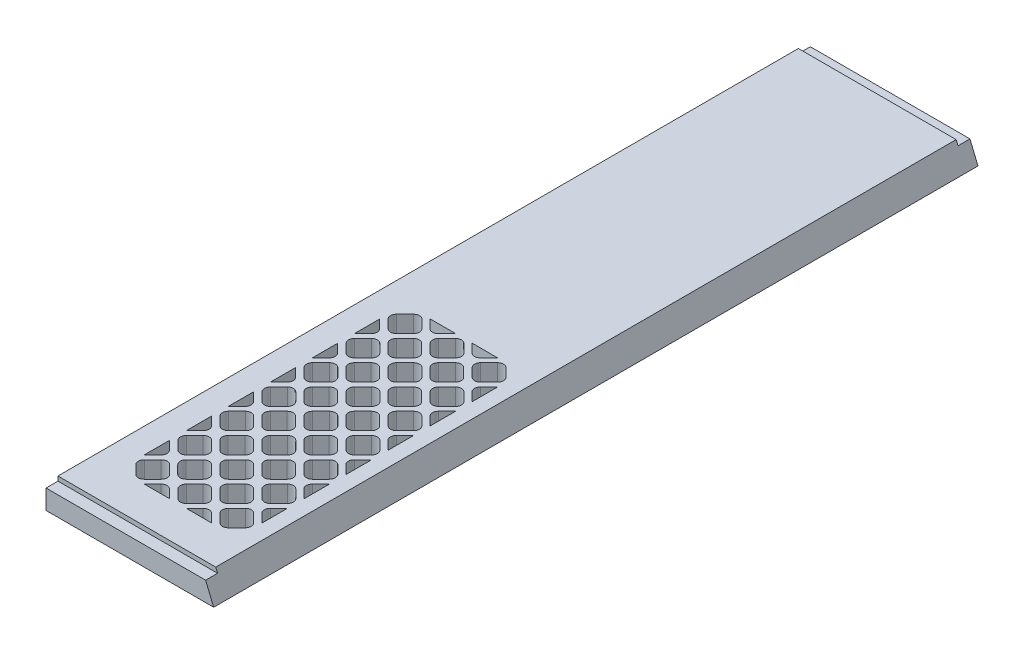
SolidWorks part; units mm, degrees
ref_plane "Front Plane" through (0, 0, 0) normal (0, 0, 1) x (1, 0, 0)
ref_plane "Top Plane" through (0, 0, 0) normal (0, 1, 0) x (1, 0, 0)
ref_plane "Right Plane" through (0, 0, 0) normal (1, 0, 0) x (0, 0, -1)
sketch "Sketch1" plane through (0, 0, 0) normal (0, 0, 1) x (1, 0, 0)
  line L0 (0, 0) -> (0, 12.7)
  line L1 (0, 12.7) -> (83.8935, 12.7)
  line L2 (83.8935, 12.7) -> (89.154, 0)
  line L3 (89.154, 0) -> (0, 0)
  dimension "D1" = 12.7
  dimension "D2" = 67.5
  dimension "D3" = 89.154
extrude "Boss-Extrude1" add sketch "Sketch1" along normal blind 406.4
sketch "Sketch2" plane through (0, 12.7, 0) normal (0, -1, 0) x (1, 0, 0)
  line L0 (0, 406.4) -> (0, 0) construction
  line L1 (0, 6.35) -> (89.154, 6.35)
  line L2 (0, 6.35) -> (0, 0)
  line L3 (0, 0) -> (89.154, 0)
  line L4 (89.154, 6.35) -> (89.154, 0)
  line L5 (89.154, 406.4) -> (89.154, 0) construction
  line L6 (0, 406.4) -> (89.154, 406.4)
  line L7 (0, 406.4) -> (0, 400.05)
  line L8 (0, 400.05) -> (89.154, 400.05)
  line L9 (89.154, 406.4) -> (89.154, 400.05)
  dimension "D1" = 6.35
  dimension "D2" = 6.35
extrude "Cut-Extrude1" cut sketch "Sketch2" along normal blind 2.3622
sketch "Sketch3" plane through (0, 0, 0) normal (0, -1, 0) x (1, 0, 0)
  line L0 (15.4898, 374.1011) -> (19.9799, 378.5912)
  line L1 (13.2447, 380.8363) -> (75.9093, 380.8363)
  line L2 (13.2447, 380.8363) -> (13.2447, 228.7637)
  line L3 (13.2447, 228.7637) -> (75.9093, 228.7637)
  line L4 (75.9093, 380.8363) -> (75.9093, 228.7637)
  line L5 (24.4701, 378.5912) -> (28.9602, 374.1011)
  line L6 (28.9602, 369.6109) -> (24.4701, 365.1208)
  line L7 (19.9799, 365.1208) -> (15.4898, 369.6109)
  line L8 (42.3319, 365.1208) -> (37.8418, 369.6109)
  line L9 (37.8418, 374.1011) -> (42.3319, 378.5912)
  line L10 (46.8221, 378.5912) -> (51.3122, 374.1011)
  line L11 (51.3122, 369.6109) -> (46.8221, 365.1208)
  line L12 (64.6839, 365.1208) -> (60.1938, 369.6109)
  line L13 (60.1938, 374.1011) -> (64.6839, 378.5912)
  line L14 (69.1741, 378.5912) -> (73.6642, 374.1011)
  line L15 (73.6642, 369.6109) -> (69.1741, 365.1208)
  line L16 (19.9799, 342.7688) -> (15.4898, 347.2589)
  line L17 (15.4898, 351.7491) -> (19.9799, 356.2392)
  line L18 (24.4701, 356.2392) -> (28.9602, 351.7491)
  line L19 (28.9602, 347.2589) -> (24.4701, 342.7688)
  line L20 (42.3319, 342.7688) -> (37.8418, 347.2589)
  line L21 (37.8418, 351.7491) -> (42.3319, 356.2392)
  line L22 (46.8221, 356.2392) -> (51.3122, 351.7491)
  line L23 (51.3122, 347.2589) -> (46.8221, 342.7688)
  line L24 (64.6839, 342.7688) -> (60.1938, 347.2589)
  line L25 (60.1938, 351.7491) -> (64.6839, 356.2392)
  line L26 (69.1741, 356.2392) -> (73.6642, 351.7491)
  line L27 (73.6642, 347.2589) -> (69.1741, 342.7688)
  line L28 (19.9799, 320.4168) -> (15.4898, 324.9069)
  line L29 (15.4898, 329.3971) -> (19.9799, 333.8872)
  line L30 (24.4701, 333.8872) -> (28.9602, 329.3971)
  line L31 (28.9602, 324.9069) -> (24.4701, 320.4168)
  line L32 (42.3319, 320.4168) -> (37.8418, 324.9069)
  line L33 (37.8418, 329.3971) -> (42.3319, 333.8872)
  line L34 (46.8221, 333.8872) -> (51.3122, 329.3971)
  line L35 (51.3122, 324.9069) -> (46.8221, 320.4168)
  line L36 (64.6839, 320.4168) -> (60.1938, 324.9069)
  line L37 (60.1938, 329.3971) -> (64.6839, 333.8872)
  line L38 (69.1741, 333.8872) -> (73.6642, 329.3971)
  line L39 (73.6642, 324.9069) -> (69.1741, 320.4168)
  line L40 (19.9799, 298.0648) -> (15.4898, 302.5549)
  line L41 (15.4898, 307.0451) -> (19.9799, 311.5352)
  line L42 (24.4701, 311.5352) -> (28.9602, 307.0451)
  line L43 (28.9602, 302.5549) -> (24.4701, 298.0648)
  line L44 (42.3319, 298.0648) -> (37.8418, 302.5549)
  line L45 (37.8418, 307.0451) -> (42.3319, 311.5352)
  line L46 (46.8221, 311.5352) -> (51.3122, 307.0451)
  line L47 (51.3122, 302.5549) -> (46.8221, 298.0648)
  line L48 (64.6839, 298.0648) -> (60.1938, 302.5549)
  line L49 (60.1938, 307.0451) -> (64.6839, 311.5352)
  line L50 (69.1741, 311.5352) -> (73.6642, 307.0451)
  line L51 (73.6642, 302.5549) -> (69.1741, 298.0648)
  line L52 (19.9799, 275.7128) -> (15.4898, 280.2029)
  line L53 (15.4898, 284.6931) -> (19.9799, 289.1832)
  line L54 (24.4701, 289.1832) -> (28.9602, 284.6931)
  line L55 (28.9602, 280.2029) -> (24.4701, 275.7128)
  line L56 (42.3319, 275.7128) -> (37.8418, 280.2029)
  line L57 (37.8418, 284.6931) -> (42.3319, 289.1832)
  line L58 (46.8221, 289.1832) -> (51.3122, 284.6931)
  line L59 (51.3122, 280.2029) -> (46.8221, 275.7128)
  line L60 (64.6839, 275.7128) -> (60.1938, 280.2029)
  line L61 (60.1938, 284.6931) -> (64.6839, 289.1832)
  line L62 (69.1741, 289.1832) -> (73.6642, 284.6931)
  line L63 (73.6642, 280.2029) -> (69.1741, 275.7128)
  line L64 (19.9799, 253.3608) -> (15.4898, 257.8509)
  line L65 (15.4898, 262.3411) -> (19.9799, 266.8312)
  line L66 (24.4701, 266.8312) -> (28.9602, 262.3411)
  line L67 (28.9602, 257.8509) -> (24.4701, 253.3608)
  line L68 (42.3319, 253.3608) -> (37.8418, 257.8509)
  line L69 (37.8418, 262.3411) -> (42.3319, 266.8312)
  line L70 (46.8221, 266.8312) -> (51.3122, 262.3411)
  line L71 (51.3122, 257.8509) -> (46.8221, 253.3608)
  line L72 (64.6839, 253.3608) -> (60.1938, 257.8509)
  line L73 (60.1938, 262.3411) -> (64.6839, 266.8312)
  line L74 (69.1741, 266.8312) -> (73.6642, 262.3411)
  line L75 (73.6642, 257.8509) -> (69.1741, 253.3608)
  line L76 (19.9799, 231.0088) -> (15.4898, 235.4989)
  line L77 (15.4898, 239.9891) -> (19.9799, 244.4792)
  line L78 (24.4701, 244.4792) -> (28.9602, 239.9891)
  line L79 (28.9602, 235.4989) -> (24.4701, 231.0088)
  line L80 (42.3319, 231.0088) -> (37.8418, 235.4989)
  line L81 (37.8418, 239.9891) -> (42.3319, 244.4792)
  line L82 (46.8221, 244.4792) -> (51.3122, 239.9891)
  line L83 (51.3122, 235.4989) -> (46.8221, 231.0088)
  line L84 (64.6839, 231.0088) -> (60.1938, 235.4989)
  line L85 (60.1938, 239.9891) -> (64.6839, 244.4792)
  line L86 (69.1741, 244.4792) -> (73.6642, 239.9891)
  line L87 (73.6642, 235.4989) -> (69.1741, 231.0088)
  line L91 (0, 400.05) -> (89.154, 400.05) construction
  line L92 (13.2447, 376.3461) -> (17.7349, 380.8363)
  line L98 (35.5967, 376.3461) -> (40.0869, 380.8363)
  line L99 (31.1066, 376.3461) -> (26.6165, 380.8363)
  line L102 (57.9487, 376.3461) -> (62.4389, 380.8363)
  line L103 (53.4586, 376.3461) -> (48.9685, 380.8363)
  line L107 (75.8106, 376.3461) -> (71.3205, 380.8363)
  line L108 (26.6165, 362.9744) -> (31.1066, 367.4645)
  line L109 (40.0869, 362.9744) -> (35.5967, 367.4645)
  line L110 (35.5967, 353.9941) -> (40.0869, 358.4843)
  line L111 (31.1066, 353.9941) -> (26.6165, 358.4843)
  line L112 (48.9685, 362.9744) -> (53.4586, 367.4645)
  line L113 (62.4389, 362.9744) -> (57.9487, 367.4645)
  line L114 (57.9487, 353.9941) -> (62.4389, 358.4843)
  line L115 (53.4586, 353.9941) -> (48.9685, 358.4843)
  line L116 (71.3205, 362.9744) -> (75.8106, 367.4645)
  line L119 (75.8106, 353.9941) -> (71.3205, 358.4843)
  line L120 (26.6165, 340.6224) -> (31.1066, 345.1125)
  line L121 (40.0869, 340.6224) -> (35.5967, 345.1125)
  line L122 (35.5967, 331.6421) -> (40.0869, 336.1323)
  line L123 (31.1066, 331.6421) -> (26.6165, 336.1323)
  line L124 (48.9685, 340.6224) -> (53.4586, 345.1125)
  line L125 (62.4389, 340.6224) -> (57.9487, 345.1125)
  line L126 (57.9487, 331.6421) -> (62.4389, 336.1323)
  line L127 (53.4586, 331.6421) -> (48.9685, 336.1323)
  line L128 (71.3205, 340.6224) -> (75.8106, 345.1125)
  line L131 (75.8106, 331.6421) -> (71.3205, 336.1323)
  line L132 (26.6165, 318.2704) -> (31.1066, 322.7605)
  line L133 (40.0869, 318.2704) -> (35.5967, 322.7605)
  line L134 (35.5967, 309.2901) -> (40.0869, 313.7803)
  line L135 (31.1066, 309.2901) -> (26.6165, 313.7803)
  line L136 (48.9685, 318.2704) -> (53.4586, 322.7605)
  line L137 (62.4389, 318.2704) -> (57.9487, 322.7605)
  line L138 (57.9487, 309.2901) -> (62.4389, 313.7803)
  line L139 (53.4586, 309.2901) -> (48.9685, 313.7803)
  line L140 (71.3205, 318.2704) -> (75.8106, 322.7605)
  line L143 (75.8106, 309.2901) -> (71.3205, 313.7803)
  line L144 (26.6165, 295.9184) -> (31.1066, 300.4085)
  line L145 (40.0869, 295.9184) -> (35.5967, 300.4085)
  line L146 (35.5967, 286.9381) -> (40.0869, 291.4283)
  line L147 (31.1066, 286.9381) -> (26.6165, 291.4283)
  line L148 (48.9685, 295.9184) -> (53.4586, 300.4085)
  line L149 (62.4389, 295.9184) -> (57.9487, 300.4085)
  line L150 (57.9487, 286.9381) -> (62.4389, 291.4283)
  line L151 (53.4586, 286.9381) -> (48.9685, 291.4283)
  line L152 (71.3205, 295.9184) -> (75.8106, 300.4085)
  line L155 (75.8106, 286.9381) -> (71.3205, 291.4283)
  line L156 (26.6165, 273.5664) -> (31.1066, 278.0565)
  line L157 (40.0869, 273.5664) -> (35.5967, 278.0565)
  line L158 (35.5967, 264.5861) -> (40.0869, 269.0763)
  line L159 (31.1066, 264.5861) -> (26.6165, 269.0763)
  line L160 (48.9685, 273.5664) -> (53.4586, 278.0565)
  line L161 (62.4389, 273.5664) -> (57.9487, 278.0565)
  line L162 (57.9487, 264.5861) -> (62.4389, 269.0763)
  line L163 (53.4586, 264.5861) -> (48.9685, 269.0763)
  line L164 (71.3205, 273.5664) -> (75.8106, 278.0565)
  line L167 (75.8106, 264.5861) -> (71.3205, 269.0763)
  line L168 (26.6165, 251.2144) -> (31.1066, 255.7045)
  line L169 (40.0869, 251.2144) -> (35.5967, 255.7045)
  line L170 (35.5967, 242.2341) -> (40.0869, 246.7243)
  line L171 (31.1066, 242.2341) -> (26.6165, 246.7243)
  line L172 (48.9685, 251.2144) -> (53.4586, 255.7045)
  line L173 (62.4389, 251.2144) -> (57.9487, 255.7045)
  line L174 (57.9487, 242.2341) -> (62.4389, 246.7243)
  line L175 (53.4586, 242.2341) -> (48.9685, 246.7243)
  line L176 (71.3205, 251.2144) -> (75.8106, 255.7045)
  line L179 (75.8106, 242.2341) -> (71.3205, 246.7243)
  line L180 (26.6165, 228.8624) -> (31.1066, 233.3525)
  line L181 (40.0869, 228.8624) -> (35.5967, 233.3525)
  line L184 (48.9685, 228.8624) -> (53.4586, 233.3525)
  line L185 (62.4389, 228.8624) -> (57.9487, 233.3525)
  line L188 (71.3205, 228.8624) -> (75.8106, 233.3525)
  line L193 (17.7349, 362.9744) -> (13.2447, 367.4645)
  line L194 (13.2447, 353.9941) -> (17.7349, 358.4843)
  line L197 (17.7349, 340.6224) -> (13.2447, 345.1125)
  line L198 (13.2447, 331.6421) -> (17.7349, 336.1323)
  line L201 (17.7349, 318.2704) -> (13.2447, 322.7605)
  line L202 (13.2447, 309.2901) -> (17.7349, 313.7803)
  line L205 (17.7349, 295.9184) -> (13.2447, 300.4085)
  line L206 (13.2447, 286.9381) -> (17.7349, 291.4283)
  line L209 (17.7349, 273.5664) -> (13.2447, 278.0565)
  line L210 (13.2447, 264.5861) -> (17.7349, 269.0763)
  line L213 (17.7349, 251.2144) -> (13.2447, 255.7045)
  line L214 (13.2447, 242.2341) -> (17.7349, 246.7243)
  line L217 (17.7349, 228.8624) -> (13.2447, 233.3525)
  line L220 (80.3007, 376.3461) -> (84.7909, 380.8363) [skipped]
  line L221 (80.3007, 353.9941) -> (84.7909, 358.4843) [skipped]
  line L222 (80.3007, 331.6421) -> (84.7909, 336.1323) [skipped]
  line L223 (80.3007, 309.2901) -> (84.7909, 313.7803) [skipped]
  line L224 (80.3007, 286.9381) -> (84.7909, 291.4283) [skipped]
  line L225 (80.3007, 264.5861) -> (84.7909, 269.0763) [skipped]
  line L226 (80.3007, 242.2341) -> (84.7909, 246.7243) [skipped]
  line L227 (80.3007, 219.8821) -> (84.7909, 224.3723) [skipped]
  line L228 (57.9487, 219.8821) -> (62.4389, 224.3723) [skipped]
  line L229 (35.5967, 219.8821) -> (40.0869, 224.3723) [skipped]
  line L230 (13.2447, 219.8821) -> (17.7349, 224.3723) [skipped]
  arc A0 (24.4701, 365.1208) -> (19.9799, 365.1208) centre (22.225, 367.3659) cw
  arc A1 (28.9602, 374.1011) -> (28.9602, 369.6109) centre (26.7151, 371.856) cw
  arc A2 (15.4898, 374.1011) -> (15.4898, 369.6109) centre (17.7349, 371.856) ccw
  arc A3 (19.9799, 378.5912) -> (24.4701, 378.5912) centre (22.225, 376.3461) cw
  arc A4 (37.8418, 374.1011) -> (37.8418, 369.6109) centre (40.0869, 371.856) ccw
  arc A5 (46.8221, 365.1208) -> (42.3319, 365.1208) centre (44.577, 367.3659) cw
  arc A6 (42.3319, 378.5912) -> (46.8221, 378.5912) centre (44.577, 376.3461) cw
  arc A7 (51.3122, 374.1011) -> (51.3122, 369.6109) centre (49.0671, 371.856) cw
  arc A8 (60.1938, 374.1011) -> (60.1938, 369.6109) centre (62.4389, 371.856) ccw
  arc A9 (69.1741, 365.1208) -> (64.6839, 365.1208) centre (66.929, 367.3659) cw
  arc A10 (64.6839, 378.5912) -> (69.1741, 378.5912) centre (66.929, 376.3461) cw
  arc A11 (73.6642, 374.1011) -> (73.6642, 369.6109) centre (71.4191, 371.856) cw
  arc A12 (15.4898, 351.7491) -> (15.4898, 347.2589) centre (17.7349, 349.504) ccw
  arc A13 (24.4701, 342.7688) -> (19.9799, 342.7688) centre (22.225, 345.0139) cw
  arc A14 (19.9799, 356.2392) -> (24.4701, 356.2392) centre (22.225, 353.9941) cw
  arc A15 (28.9602, 351.7491) -> (28.9602, 347.2589) centre (26.7151, 349.504) cw
  arc A16 (37.8418, 351.7491) -> (37.8418, 347.2589) centre (40.0869, 349.504) ccw
  arc A17 (42.3319, 356.2392) -> (46.8221, 356.2392) centre (44.577, 353.9941) cw
  arc A18 (51.3122, 351.7491) -> (51.3122, 347.2589) centre (49.0671, 349.504) cw
  arc A19 (46.8221, 342.7688) -> (42.3319, 342.7688) centre (44.577, 345.0139) cw
  arc A20 (60.1938, 351.7491) -> (60.1938, 347.2589) centre (62.4389, 349.504) ccw
  arc A21 (64.6839, 356.2392) -> (69.1741, 356.2392) centre (66.929, 353.9941) cw
  arc A22 (73.6642, 351.7491) -> (73.6642, 347.2589) centre (71.4191, 349.504) cw
  arc A23 (69.1741, 342.7688) -> (64.6839, 342.7688) centre (66.929, 345.0139) cw
  arc A24 (15.4898, 329.3971) -> (15.4898, 324.9069) centre (17.7349, 327.152) ccw
  arc A25 (24.4701, 320.4168) -> (19.9799, 320.4168) centre (22.225, 322.6619) cw
  arc A26 (19.9799, 333.8872) -> (24.4701, 333.8872) centre (22.225, 331.6421) cw
  arc A27 (28.9602, 329.3971) -> (28.9602, 324.9069) centre (26.7151, 327.152) cw
  arc A28 (37.8418, 329.3971) -> (37.8418, 324.9069) centre (40.0869, 327.152) ccw
  arc A29 (42.3319, 333.8872) -> (46.8221, 333.8872) centre (44.577, 331.6421) cw
  arc A30 (51.3122, 329.3971) -> (51.3122, 324.9069) centre (49.0671, 327.152) cw
  arc A31 (46.8221, 320.4168) -> (42.3319, 320.4168) centre (44.577, 322.6619) cw
  arc A32 (60.1938, 329.3971) -> (60.1938, 324.9069) centre (62.4389, 327.152) ccw
  arc A33 (64.6839, 333.8872) -> (69.1741, 333.8872) centre (66.929, 331.6421) cw
  arc A34 (73.6642, 329.3971) -> (73.6642, 324.9069) centre (71.4191, 327.152) cw
  arc A35 (69.1741, 320.4168) -> (64.6839, 320.4168) centre (66.929, 322.6619) cw
  arc A36 (15.4898, 307.0451) -> (15.4898, 302.5549) centre (17.7349, 304.8) ccw
  arc A37 (24.4701, 298.0648) -> (19.9799, 298.0648) centre (22.225, 300.3099) cw
  arc A38 (19.9799, 311.5352) -> (24.4701, 311.5352) centre (22.225, 309.2901) cw
  arc A39 (28.9602, 307.0451) -> (28.9602, 302.5549) centre (26.7151, 304.8) cw
  arc A40 (37.8418, 307.0451) -> (37.8418, 302.5549) centre (40.0869, 304.8) ccw
  arc A41 (42.3319, 311.5352) -> (46.8221, 311.5352) centre (44.577, 309.2901) cw
  arc A42 (51.3122, 307.0451) -> (51.3122, 302.5549) centre (49.0671, 304.8) cw
  arc A43 (46.8221, 298.0648) -> (42.3319, 298.0648) centre (44.577, 300.3099) cw
  arc A44 (60.1938, 307.0451) -> (60.1938, 302.5549) centre (62.4389, 304.8) ccw
  arc A45 (64.6839, 311.5352) -> (69.1741, 311.5352) centre (66.929, 309.2901) cw
  arc A46 (73.6642, 307.0451) -> (73.6642, 302.5549) centre (71.4191, 304.8) cw
  arc A47 (69.1741, 298.0648) -> (64.6839, 298.0648) centre (66.929, 300.3099) cw
  arc A48 (15.4898, 284.6931) -> (15.4898, 280.2029) centre (17.7349, 282.448) ccw
  arc A49 (24.4701, 275.7128) -> (19.9799, 275.7128) centre (22.225, 277.9579) cw
  arc A50 (19.9799, 289.1832) -> (24.4701, 289.1832) centre (22.225, 286.9381) cw
  arc A51 (28.9602, 284.6931) -> (28.9602, 280.2029) centre (26.7151, 282.448) cw
  arc A52 (37.8418, 284.6931) -> (37.8418, 280.2029) centre (40.0869, 282.448) ccw
  arc A53 (42.3319, 289.1832) -> (46.8221, 289.1832) centre (44.577, 286.9381) cw
  arc A54 (51.3122, 284.6931) -> (51.3122, 280.2029) centre (49.0671, 282.448) cw
  arc A55 (46.8221, 275.7128) -> (42.3319, 275.7128) centre (44.577, 277.9579) cw
  arc A56 (60.1938, 284.6931) -> (60.1938, 280.2029) centre (62.4389, 282.448) ccw
  arc A57 (64.6839, 289.1832) -> (69.1741, 289.1832) centre (66.929, 286.9381) cw
  arc A58 (73.6642, 284.6931) -> (73.6642, 280.2029) centre (71.4191, 282.448) cw
  arc A59 (69.1741, 275.7128) -> (64.6839, 275.7128) centre (66.929, 277.9579) cw
  arc A60 (15.4898, 262.3411) -> (15.4898, 257.8509) centre (17.7349, 260.096) ccw
  arc A61 (24.4701, 253.3608) -> (19.9799, 253.3608) centre (22.225, 255.6059) cw
  arc A62 (19.9799, 266.8312) -> (24.4701, 266.8312) centre (22.225, 264.5861) cw
  arc A63 (28.9602, 262.3411) -> (28.9602, 257.8509) centre (26.7151, 260.096) cw
  arc A64 (37.8418, 262.3411) -> (37.8418, 257.8509) centre (40.0869, 260.096) ccw
  arc A65 (42.3319, 266.8312) -> (46.8221, 266.8312) centre (44.577, 264.5861) cw
  arc A66 (51.3122, 262.3411) -> (51.3122, 257.8509) centre (49.0671, 260.096) cw
  arc A67 (46.8221, 253.3608) -> (42.3319, 253.3608) centre (44.577, 255.6059) cw
  arc A68 (60.1938, 262.3411) -> (60.1938, 257.8509) centre (62.4389, 260.096) ccw
  arc A69 (64.6839, 266.8312) -> (69.1741, 266.8312) centre (66.929, 264.5861) cw
  arc A70 (73.6642, 262.3411) -> (73.6642, 257.8509) centre (71.4191, 260.096) cw
  arc A71 (69.1741, 253.3608) -> (64.6839, 253.3608) centre (66.929, 255.6059) cw
  arc A72 (15.4898, 239.9891) -> (15.4898, 235.4989) centre (17.7349, 237.744) ccw
  arc A73 (24.4701, 231.0088) -> (19.9799, 231.0088) centre (22.225, 233.2539) cw
  arc A74 (19.9799, 244.4792) -> (24.4701, 244.4792) centre (22.225, 242.2341) cw
  arc A75 (28.9602, 239.9891) -> (28.9602, 235.4989) centre (26.7151, 237.744) cw
  arc A76 (37.8418, 239.9891) -> (37.8418, 235.4989) centre (40.0869, 237.744) ccw
  arc A77 (42.3319, 244.4792) -> (46.8221, 244.4792) centre (44.577, 242.2341) cw
  arc A78 (51.3122, 239.9891) -> (51.3122, 235.4989) centre (49.0671, 237.744) cw
  arc A79 (46.8221, 231.0088) -> (42.3319, 231.0088) centre (44.577, 233.2539) cw
  arc A80 (60.1938, 239.9891) -> (60.1938, 235.4989) centre (62.4389, 237.744) ccw
  arc A81 (64.6839, 244.4792) -> (69.1741, 244.4792) centre (66.929, 242.2341) cw
  arc A82 (73.6642, 239.9891) -> (73.6642, 235.4989) centre (71.4191, 237.744) cw
  arc A83 (69.1741, 231.0088) -> (64.6839, 231.0088) centre (66.929, 233.2539) cw
  arc A91 (35.5967, 376.3461) -> (31.1066, 376.3461) centre (33.3517, 378.5912) cw
  arc A95 (57.9487, 376.3461) -> (53.4586, 376.3461) centre (55.7037, 378.5912) cw
  arc A99 (75.9093, 376.2516) -> (75.8106, 376.3461) centre (78.0557, 378.5912) cw
  arc A100 (35.5967, 367.4645) -> (31.1066, 367.4645) centre (33.3517, 365.2194) ccw
  arc A101 (26.6165, 358.4843) -> (26.6165, 362.9744) centre (28.8616, 360.7293) cw
  arc A102 (40.0869, 358.4843) -> (40.0869, 362.9744) centre (37.8418, 360.7293) ccw
  arc A103 (35.5967, 353.9941) -> (31.1066, 353.9941) centre (33.3517, 356.2392) cw
  arc A104 (57.9487, 367.4645) -> (53.4586, 367.4645) centre (55.7037, 365.2194) ccw
  arc A105 (48.9685, 358.4843) -> (48.9685, 362.9744) centre (51.2136, 360.7293) cw
  arc A106 (62.4389, 358.4843) -> (62.4389, 362.9744) centre (60.1938, 360.7293) ccw
  arc A107 (57.9487, 353.9941) -> (53.4586, 353.9941) centre (55.7037, 356.2392) cw
  arc A108 (75.9093, 367.559) -> (75.8106, 367.4645) centre (78.0557, 365.2194) ccw
  arc A109 (71.3205, 358.4843) -> (71.3205, 362.9744) centre (73.5656, 360.7293) cw
  arc A111 (75.9093, 353.8996) -> (75.8106, 353.9941) centre (78.0557, 356.2392) cw
  arc A112 (35.5967, 345.1125) -> (31.1066, 345.1125) centre (33.3517, 342.8674) ccw
  arc A113 (26.6165, 336.1323) -> (26.6165, 340.6224) centre (28.8616, 338.3773) cw
  arc A114 (40.0869, 336.1323) -> (40.0869, 340.6224) centre (37.8418, 338.3773) ccw
  arc A115 (35.5967, 331.6421) -> (31.1066, 331.6421) centre (33.3517, 333.8872) cw
  arc A116 (57.9487, 345.1125) -> (53.4586, 345.1125) centre (55.7037, 342.8674) ccw
  arc A117 (48.9685, 336.1323) -> (48.9685, 340.6224) centre (51.2136, 338.3773) cw
  arc A118 (62.4389, 336.1323) -> (62.4389, 340.6224) centre (60.1938, 338.3773) ccw
  arc A119 (57.9487, 331.6421) -> (53.4586, 331.6421) centre (55.7037, 333.8872) cw
  arc A120 (75.9093, 345.207) -> (75.8106, 345.1125) centre (78.0557, 342.8674) ccw
  arc A121 (71.3205, 336.1323) -> (71.3205, 340.6224) centre (73.5656, 338.3773) cw
  arc A123 (75.9093, 331.5476) -> (75.8106, 331.6421) centre (78.0557, 333.8872) cw
  arc A124 (35.5967, 322.7605) -> (31.1066, 322.7605) centre (33.3517, 320.5154) ccw
  arc A125 (26.6165, 313.7803) -> (26.6165, 318.2704) centre (28.8616, 316.0253) cw
  arc A126 (40.0869, 313.7803) -> (40.0869, 318.2704) centre (37.8418, 316.0253) ccw
  arc A127 (35.5967, 309.2901) -> (31.1066, 309.2901) centre (33.3517, 311.5352) cw
  arc A128 (57.9487, 322.7605) -> (53.4586, 322.7605) centre (55.7037, 320.5154) ccw
  arc A129 (48.9685, 313.7803) -> (48.9685, 318.2704) centre (51.2136, 316.0253) cw
  arc A130 (62.4389, 313.7803) -> (62.4389, 318.2704) centre (60.1938, 316.0253) ccw
  arc A131 (57.9487, 309.2901) -> (53.4586, 309.2901) centre (55.7037, 311.5352) cw
  arc A132 (75.9093, 322.855) -> (75.8106, 322.7605) centre (78.0557, 320.5154) ccw
  arc A133 (71.3205, 313.7803) -> (71.3205, 318.2704) centre (73.5656, 316.0253) cw
  arc A135 (75.9093, 309.1956) -> (75.8106, 309.2901) centre (78.0557, 311.5352) cw
  arc A136 (35.5967, 300.4085) -> (31.1066, 300.4085) centre (33.3517, 298.1634) ccw
  arc A137 (26.6165, 291.4283) -> (26.6165, 295.9184) centre (28.8616, 293.6733) cw
  arc A138 (40.0869, 291.4283) -> (40.0869, 295.9184) centre (37.8418, 293.6733) ccw
  arc A139 (35.5967, 286.9381) -> (31.1066, 286.9381) centre (33.3517, 289.1832) cw
  arc A140 (57.9487, 300.4085) -> (53.4586, 300.4085) centre (55.7037, 298.1634) ccw
  arc A141 (48.9685, 291.4283) -> (48.9685, 295.9184) centre (51.2136, 293.6733) cw
  arc A142 (62.4389, 291.4283) -> (62.4389, 295.9184) centre (60.1938, 293.6733) ccw
  arc A143 (57.9487, 286.9381) -> (53.4586, 286.9381) centre (55.7037, 289.1832) cw
  arc A144 (75.9093, 300.503) -> (75.8106, 300.4085) centre (78.0557, 298.1634) ccw
  arc A145 (71.3205, 291.4283) -> (71.3205, 295.9184) centre (73.5656, 293.6733) cw
  arc A147 (75.9093, 286.8436) -> (75.8106, 286.9381) centre (78.0557, 289.1832) cw
  arc A148 (35.5967, 278.0565) -> (31.1066, 278.0565) centre (33.3517, 275.8114) ccw
  arc A149 (26.6165, 269.0763) -> (26.6165, 273.5664) centre (28.8616, 271.3213) cw
  arc A150 (40.0869, 269.0763) -> (40.0869, 273.5664) centre (37.8418, 271.3213) ccw
  arc A151 (35.5967, 264.5861) -> (31.1066, 264.5861) centre (33.3517, 266.8312) cw
  arc A152 (57.9487, 278.0565) -> (53.4586, 278.0565) centre (55.7037, 275.8114) ccw
  arc A153 (48.9685, 269.0763) -> (48.9685, 273.5664) centre (51.2136, 271.3213) cw
  arc A154 (62.4389, 269.0763) -> (62.4389, 273.5664) centre (60.1938, 271.3213) ccw
  arc A155 (57.9487, 264.5861) -> (53.4586, 264.5861) centre (55.7037, 266.8312) cw
  arc A156 (75.9093, 278.151) -> (75.8106, 278.0565) centre (78.0557, 275.8114) ccw
  arc A157 (71.3205, 269.0763) -> (71.3205, 273.5664) centre (73.5656, 271.3213) cw
  arc A159 (75.9093, 264.4916) -> (75.8106, 264.5861) centre (78.0557, 266.8312) cw
  arc A160 (35.5967, 255.7045) -> (31.1066, 255.7045) centre (33.3517, 253.4594) ccw
  arc A161 (26.6165, 246.7243) -> (26.6165, 251.2144) centre (28.8616, 248.9693) cw
  arc A162 (40.0869, 246.7243) -> (40.0869, 251.2144) centre (37.8418, 248.9693) ccw
  arc A163 (35.5967, 242.2341) -> (31.1066, 242.2341) centre (33.3517, 244.4792) cw
  arc A164 (57.9487, 255.7045) -> (53.4586, 255.7045) centre (55.7037, 253.4594) ccw
  arc A165 (48.9685, 246.7243) -> (48.9685, 251.2144) centre (51.2136, 248.9693) cw
  arc A166 (62.4389, 246.7243) -> (62.4389, 251.2144) centre (60.1938, 248.9693) ccw
  arc A167 (57.9487, 242.2341) -> (53.4586, 242.2341) centre (55.7037, 244.4792) cw
  arc A168 (75.9093, 255.799) -> (75.8106, 255.7045) centre (78.0557, 253.4594) ccw
  arc A169 (71.3205, 246.7243) -> (71.3205, 251.2144) centre (73.5656, 248.9693) cw
  arc A171 (75.9093, 242.1396) -> (75.8106, 242.2341) centre (78.0557, 244.4792) cw
  arc A172 (35.5967, 233.3525) -> (31.1066, 233.3525) centre (33.3517, 231.1074) ccw
  arc A173 (26.522, 228.7637) -> (26.6165, 228.8624) centre (28.8616, 226.6173) cw
  arc A174 (40.1814, 228.7637) -> (40.0869, 228.8624) centre (37.8418, 226.6173) ccw
  arc A176 (57.9487, 233.3525) -> (53.4586, 233.3525) centre (55.7037, 231.1074) ccw
  arc A177 (48.874, 228.7637) -> (48.9685, 228.8624) centre (51.2136, 226.6173) cw
  arc A178 (62.5334, 228.7637) -> (62.4389, 228.8624) centre (60.1938, 226.6173) ccw
  arc A180 (75.9093, 233.447) -> (75.8106, 233.3525) centre (78.0557, 231.1074) ccw
  arc A181 (71.226, 228.7637) -> (71.3205, 228.8624) centre (73.5656, 226.6173) cw
  arc A186 (17.7349, 358.4843) -> (17.7349, 362.9744) centre (15.4898, 360.7293) ccw
  arc A190 (17.7349, 336.1323) -> (17.7349, 340.6224) centre (15.4898, 338.3773) ccw
  arc A194 (17.7349, 313.7803) -> (17.7349, 318.2704) centre (15.4898, 316.0253) ccw
  arc A198 (17.7349, 291.4283) -> (17.7349, 295.9184) centre (15.4898, 293.6733) ccw
  arc A202 (17.7349, 269.0763) -> (17.7349, 273.5664) centre (15.4898, 271.3213) ccw
  arc A206 (17.7349, 246.7243) -> (17.7349, 251.2144) centre (15.4898, 248.9693) ccw
  arc A210 (17.8294, 228.7637) -> (17.7349, 228.8624) centre (15.4898, 226.6173) ccw
  point P11 (22.225, 362.8757)
  point P16 (13.2447, 371.856)
  point P19 (22.225, 380.8363)
  point P44 (44.577, 380.8363)
  point P45 (13.2447, 304.8)
  point P272 (44.577, 400.05)
  point P281 (10.9997, 374.1011)
  point P284 (2.0194, 383.0813)
  point P287 (10.9997, 392.0616)
  dimension "D4" = 3.175
  dimension "D1" = 12.7
  dimension "D2" = 45
  dimension "D3" = 12.7
  dimension "D8" = 12.7
  dimension "D9" = 12.7
  dimension "D10" = 3.175
  dimension "D5" = 3
  dimension "D7" = 7
extrude "Cut-Extrude3" cut sketch "Sketch3" against normal through all contours A3 L0 A2 L7 A0 L6 A1 L5 | A7 L10 A6 L9 A4 L8 A5 L11 | A11 L14 A10 L13 A8 L12 A9 L15 | A91 L98 L1 L99 | L194 A186 L193 L2 | A103 L110 A102 L109 A100 L108 A101 L111 | A107 L114 A106 L113 A104 L112 A105 L115 | A111 L4 A108 L116 A109 L119 | A15 L18 A14 L17 A12 L16 A13 L19 | A19 L23 A18 L22 A17 L21 A16 L20 | A23 L27 A22 L26 A21 L25 A20 L24 | A123 L4 A120 L128 A121 L131 | A119 L126 A118 L125 A116 L124 A117 L127 | A115 L122 A114 L121 A112 L120 A113 L123 | L198 A190 L197 L2 | A27 L30 A26 L29 A24 L28 A25 L31 | A31 L35 A30 L34 A29 L33 A28 L32 | A35 L39 A34 L38 A33 L37 A32 L36 | A131 L138 A130 L137 A128 L136 A129 L139 | A135 L4 A132 L140 A133 L143 | A95 L102 L1 L103 | A127 L134 A126 L133 A124 L132 A125 L135 | L202 A194 L201 L2 | A39 L42 A38 L41 A36 L40 A37 L43 | A43 L47 A42 L46 A41 L45 A40 L44 | A47 L51 A46 L50 A45 L49 A44 L48 | L206 A198 L205 L2 | A51 L54 A50 L53 A48 L52 A49 L55 | A139 L146 A138 L145 A136 L144 A137 L147 | A55 L59 A54 L58 A53 L57 A52 L56 | A143 L150 A142 L149 A140 L148 A141 L151 | A147 L4 A144 L152 A145 L155 | A59 L63 A58 L62 A57 L61 A56 L60 | L210 A202 L209 L2 | A151 L158 A150 L157 A148 L156 A149 L159 | A155 L162 A154 L161 A152 L160 A153 L163 | A159 L4 A156 L164 A157 L167 | A71 L75 A70 L74 A69 L73 A68 L72 | A67 L71 A66 L70 A65 L69 A64 L68 | A63 L66 A62 L65 A60 L64 A61 L67 | L214 A206 L213 L2 | A75 L78 A74 L77 A72 L76 A73 L79 | A163 L170 A162 L169 A160 L168 A161 L171 | L3 A174 L181 A172 L180 A173 | A79 L83 A78 L82 A77 L81 A76 L80 | A167 L174 A166 L173 A164 L172 A165 L175 | A171 L4 A168 L176 A169 L179 | A83 L87 A82 L86 A81 L85 A80 L84 | L3 A178 L185 A176 L184 A177 region at (22.225, 0, 371.856) region at (33.3517, 0, 378.7658) region at (15.3152, 0, 360.7293) region at (55.7037, 0, 378.7658) region at (15.3152, 0, 338.3773) region at (15.3152, 0, 316.0253) region at (15.3152, 0, 293.6733) region at (73.8039, 0, 360.7293) region at (15.3152, 0, 271.3213) region at (73.8039, 0, 338.3773) region at (15.3152, 0, 248.9693) region at (73.8039, 0, 316.0253) region at (73.8039, 0, 293.6733) region at (73.8039, 0, 271.3213) region at (33.3517, 0, 230.8691) region at (73.8039, 0, 248.9693) region at (55.7037, 0, 230.8691) region at (44.577, 0, 371.856) region at (66.929, 0, 371.856) region at (22.225, 0, 349.504) region at (44.577, 0, 349.504) region at (66.929, 0, 349.504) region at (22.225, 0, 327.152) region at (44.577, 0, 327.152) region at (66.929, 0, 327.152) region at (22.225, 0, 304.8) region at (44.577, 0, 304.8) region at (66.929, 0, 304.8) region at (22.225, 0, 282.448) region at (44.577, 0, 282.448) region at (66.929, 0, 282.448) region at (22.225, 0, 260.096) region at (44.577, 0, 260.096) region at (66.929, 0, 260.096) region at (22.225, 0, 237.744) region at (44.577, 0, 237.744) region at (66.929, 0, 237.744) region at (33.3517, 0, 360.7293) region at (55.7037, 0, 360.7293) region at (33.3517, 0, 338.3773) region at (55.7037, 0, 338.3773) region at (33.3517, 0, 316.0253) region at (55.7037, 0, 316.0253) region at (33.3517, 0, 293.6733) region at (55.7037, 0, 293.6733) region at (33.3517, 0, 271.3213) region at (55.7037, 0, 271.3213) region at (33.3517, 0, 248.9693) region at (55.7037, 0, 248.9693)
